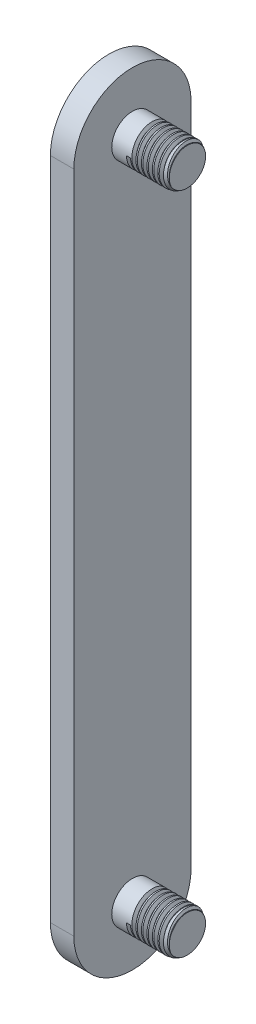
SolidWorks part; units mm, degrees
ref_plane "정면" through (0, 0, 0) normal (0, 0, 1) x (1, 0, 0)
ref_plane "윗면" through (0, 0, 0) normal (0, 1, 0) x (1, 0, 0)
ref_plane "우측면" through (0, 0, 0) normal (1, 0, 0) x (0, 0, -1)
sketch "스케치1" plane through (0, 0, 0) normal (1, 0, 0) x (0, 0, -1)
  line L0 (-233.0738, 0) -> (233.0738, 0) construction
  line L1 (0, 234.732) -> (0, -234.732) construction
  line L2 (0, -85) -> (0, 0)
  line L3 (15, -85) -> (15, 0)
  arc A0 (0, 0) -> (15, 0) centre (7.5, 0) cw
  arc A1 (15, -85) -> (0, -85) centre (7.5, -85) cw
  circle A2 centre (7.5, -85) radius 2.65
  circle A3 centre (7.5, 0) radius 2.65
  point P5 (0, 0)
  point P6 (0, 0)
  dimension "D1" = 15
  dimension "D2" = 5.3
  dimension "D3" = 5.3
  dimension "D4" = 85
extrude "보스-돌출1" add sketch "스케치1" along normal blind 10 contours A3 | A2
extrude "보스-돌출2" add sketch "스케치1<3>" along normal blind 3
sketch "스케치1<3>" plane through (0, 0, 0) normal (1, 0, 0) x (0, 0, -1) same geometry as "스케치1"
ref_plane "평면2" through (10.5, 0, 0) normal (1, 0, 0) x (0, 0, -1)
ref_plane "평면4" through (11, 0, 0) normal (1, 0, 0) x (0, 0, -1)
chamfer "모따기3" distance 0.5 angle 30 2 edges at (10, 0, -10.15) (10, -85, -10.15) first distance on face at (10, 0, -10.15) first distance on face at (10, -85, -10.15)
thread "나사산2" pitch 0.7 method cut profile "나사산 프로파일2" start angle 0, offset 0, length 0, pitch 0.7, diameter 5.3
ref_plane "평면5" through (11, 0, -4.85) normal (0, 1, 0) x (0, 0, -1)
sketch "나사산 프로파일2" plane through (11, 0, -4.85) normal (0, 1, 0) x (0, 0, -1)
  line L0 (0, 0) -> (0, 0.7) construction
  line L1 (0, 0) -> (0.3789, 0.2187)
  line L2 (0.3789, 0.2187) -> (0.3789, 0.3062)
  line L3 (0.3789, 0.3062) -> (0, 0.525)
  line L4 (0.3789, 0.2625) -> (0, 0.2625) construction
  line L11 (0, 0) -> (0, 0.525)
  point P2 (0, 0)
  dimension "Pitch" = 0.7
  dimension "Profile_Angle" = 60
  dimension "Profile_Land" = 0.0875
  dimension "Profile_Height" = 0.3789
thread "나사산3" pitch 0.7 method cut profile "나사산 프로파일3" start angle 0, offset 0, length 0, pitch 0.7, diameter 5.3
ref_plane "평면6" through (11, -85, -4.85) normal (0, 1, 0) x (0, 0, -1)
sketch "나사산 프로파일3" plane through (11, -85, -4.85) normal (0, 1, 0) x (0, 0, -1)
  line L0 (0, 0) -> (0, 0.7) construction
  line L1 (0, 0) -> (0.3789, 0.2187)
  line L2 (0.3789, 0.2187) -> (0.3789, 0.3062)
  line L3 (0.3789, 0.3062) -> (0, 0.525)
  line L4 (0.3789, 0.2625) -> (0, 0.2625) construction
  line L11 (0, 0) -> (0, 0.525)
  point P2 (0, 0)
  dimension "Pitch" = 0.7
  dimension "Profile_Angle" = 60
  dimension "Profile_Land" = 0.0875
  dimension "Profile_Height" = 0.3789
